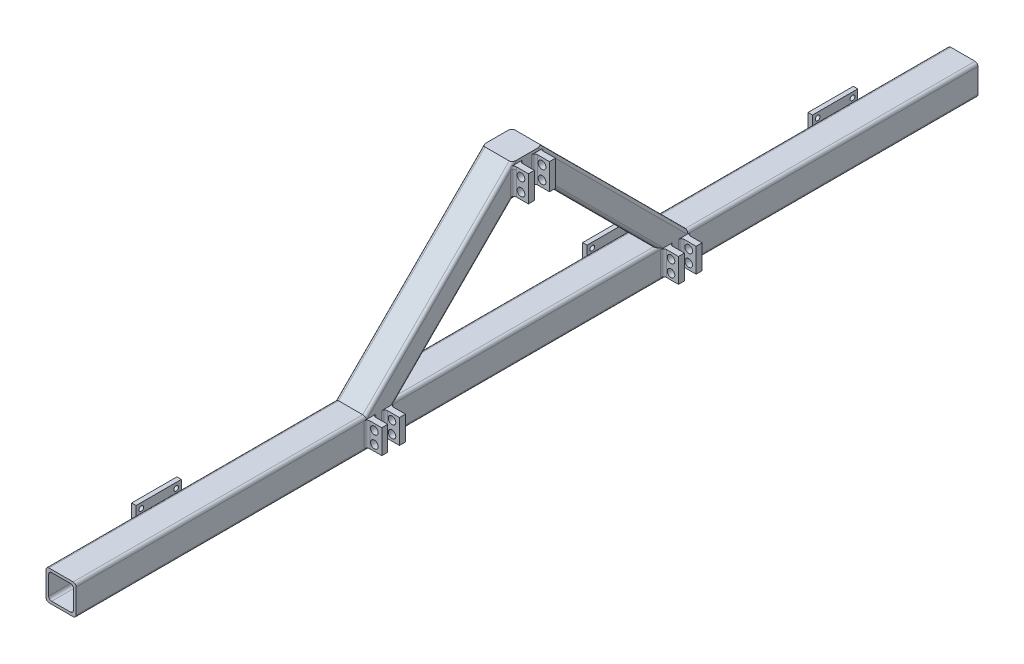
SolidWorks part; units mm, degrees
ref_plane "Alzado" through (0, 0, 0) normal (0, 0, 1) x (1, 0, 0)
ref_plane "Planta" through (0, 0, 0) normal (0, 1, 0) x (1, 0, 0)
ref_plane "Vista lateral" through (0, 0, 0) normal (1, 0, 0) x (0, 0, -1)
sketch "Croquis1" plane through (0, 0, 0) normal (0, 0, 1) x (1, 0, 0)
  line L1 (-40.8, 50.8) -> (40.8, 50.8)
  line L2 (-50.8, 40.8) -> (-50.8, -40.8)
  line L3 (-40.8, -50.8) -> (40.8, -50.8)
  line L4 (50.8, 40.8) -> (50.8, -40.8)
  line L5 (-31.8, 41.8) -> (31.8, 41.8)
  line L6 (-41.8, 31.8) -> (-41.8, -31.8)
  line L7 (-31.8, -41.8) -> (31.8, -41.8)
  line L8 (41.8, 31.8) -> (41.8, -31.8)
  arc A0 (40.8, -50.8) -> (50.8, -40.8) centre (40.8, -40.8) ccw
  arc A1 (31.8, -41.8) -> (41.8, -31.8) centre (31.8, -31.8) ccw
  arc A2 (-41.8, -31.8) -> (-31.8, -41.8) centre (-31.8, -31.8) ccw
  arc A3 (-50.8, -40.8) -> (-40.8, -50.8) centre (-40.8, -40.8) ccw
  arc A4 (31.8, 41.8) -> (41.8, 31.8) centre (31.8, 31.8) cw
  arc A5 (40.8, 50.8) -> (50.8, 40.8) centre (40.8, 40.8) cw
  arc A6 (-40.8, 50.8) -> (-50.8, 40.8) centre (-40.8, 40.8) ccw
  arc A7 (-31.8, 41.8) -> (-41.8, 31.8) centre (-31.8, 31.8) ccw
  point P8 (0, 41.8)
  point P10 (0, 50.8)
  point P11 (-41.8, 0)
  point P24 (50.8, 50.8)
  point P27 (-50.8, 50.8)
  dimension "D5" = 10
  dimension "D1" = 9
  dimension "D2" = 9
  dimension "D3" = 9
  dimension "D4" = 101.6
extrude "Saliente-Extruir1" add sketch "Croquis1" along normal blind 3040
sketch "Croquis2" plane through (50.8, 0, 0) normal (1, 0, 0) x (0, 0, -1)
  line L0 (0, 0) -> (-3040, 0) construction
  line L1 (-3040, -40.8) -> (-3040, 40.8) construction
  line L2 (-2073.8815, 40.8) -> (-1570, 544.6815)
  line L3 (-3040, 40.8) -> (0, 40.8) construction
  line L4 (-1570, 544.6815) -> (-1470, 544.6815)
  line L5 (-1470, 544.6815) -> (-966.1185, 40.8)
  line L6 (-1966.1185, 40.8) -> (-1570, 436.9185)
  line L7 (-1570, 436.9185) -> (-1470, 436.9185)
  line L8 (-1470, 436.9185) -> (-1073.8815, 40.8)
  line L9 (-1073.8815, 40.8) -> (-966.1185, 40.8)
  line L10 (-2073.8815, 40.8) -> (-1966.1185, 40.8)
  point P9 (-1520, 544.6815)
  point P12 (-1520, 0)
  point P13 (-2020, 40.8)
  point P16 (-1020, 40.8)
  dimension "D1" = 100
  dimension "D2" = 1000
  dimension "D3" = 76.2
  dimension "D4" = 45
extrude "Saliente-Extruir2" add sketch "Croquis2" against normal up to vertex (101.6 mm away) up to point (-50.8, 40.8, 3040)
fillet "Redondeo1" radius 10 1 edges at (-50.8, 292.7408, 1821.9408)
fillet "Redondeo2" radius 10 8 edges at (-50.8, 238.8592, 1271.9408) (-50.8, 436.9185, 1520) (50.8, 238.8592, 1768.0592) (50.8, 436.9185, 1520) (50.8, 238.8592, 1271.9408) (50.8, 292.7408, 1218.0592) (-50.8, 292.7408, 1218.0592) (50.8, 292.7408, 1821.9408)
sketch "Croquis3" plane through (50.8, 0, 0) normal (1, 0, 0) x (0, 0, -1)
  line L0 (-1574.1421, 446.9185) -> (-1465.8579, 446.9185) construction
  line L1 (-1565.5, 535.0394) -> (-1545.5, 535.0394)
  line L2 (-1565.5, 535.0394) -> (-1565.5, 446.9185)
  line L3 (-1565.5, 446.9185) -> (-1545.5, 446.9185)
  line L4 (-1545.5, 535.0394) -> (-1545.5, 446.9185)
  line L6 (-1494.5, 535.0394) -> (-1474.5, 535.0394)
  line L7 (-1494.5, 535.0394) -> (-1494.5, 446.9185)
  line L8 (-1494.5, 446.9185) -> (-1474.5, 446.9185)
  line L9 (-1474.5, 535.0394) -> (-1474.5, 446.9185)
  line L11 (-980.2606, 40.8) -> (-1484.1421, 544.6815) construction
  line L12 (-1555.8579, 544.6815) -> (-2059.7394, 40.8) construction
  dimension "D1" = 51
  dimension "D2" = 20
extrude "Saliente-Extruir3" add sketch "Croquis3" along normal blind 50
sketch "Croquis4" plane through (0, 0, 1565.5) normal (0, 0, 1) x (1, 0, 0)
  line L0 (75.8, 535.0394) -> (75.8, 446.9185) construction
  line L1 (100.8, 535.0394) -> (50.8, 535.0394) construction
  line L2 (100.8, 446.9185) -> (50.8, 446.9185) construction
  line L3 (50.8, 490.9789) -> (100.8, 490.9789) construction
  line L4 (50.8, 535.0394) -> (50.8, 446.9185) construction
  line L5 (100.8, 535.0394) -> (100.8, 446.9185) construction
  circle A0 centre (75.8, 513.0089) radius 13
  circle A1 centre (75.8, 468.9489) radius 13
  dimension "D1" = 26
  dimension "D2" = 44.06
extrude "Cortar-Extruir1" cut sketch "Croquis4" against normal through all
sketch "Croquis5" plane through (-50.8, 0, 0) normal (-1, 0, 0) x (0, 0, 1)
  line L0 (0, 0) -> (760, 0) construction
  line L1 (760, 0) -> (1520, 0) construction
  line L2 (1520, 0) -> (2280, 0) construction
  line L3 (2280, 0) -> (3040, 0) construction
  line L4 (3040, 40.8) -> (3040, -40.8) construction
  line L5 (976.1185, 50.8) -> (0, 50.8) construction
  line L6 (456.2, -76.2) -> (303.8, -76.2)
  line L7 (456.2, -76.2) -> (456.2, 76.2)
  line L8 (456.2, 76.2) -> (303.8, 76.2)
  line L9 (303.8, -76.2) -> (303.8, 76.2)
  line L10 (456.2, -76.2) -> (303.8, 76.2) construction
  line L11 (456.2, 76.2) -> (303.8, -76.2) construction
  line L12 (1216.2, -76.2) -> (1216.2, 76.2)
  line L13 (1216.2, -76.2) -> (1063.8, -76.2)
  line L14 (1063.8, -76.2) -> (1063.8, 76.2)
  line L15 (1216.2, 76.2) -> (1063.8, 76.2)
  line L16 (1976.2, -76.2) -> (1976.2, 76.2)
  line L17 (1976.2, -76.2) -> (1823.8, -76.2)
  line L18 (1823.8, -76.2) -> (1823.8, 76.2)
  line L19 (1976.2, 76.2) -> (1823.8, 76.2)
  line L20 (2736.2, -76.2) -> (2736.2, 76.2)
  line L21 (2736.2, -76.2) -> (2583.8, -76.2)
  line L22 (2583.8, -76.2) -> (2583.8, 76.2)
  line L23 (2736.2, 76.2) -> (2583.8, 76.2)
  line L24 (456.2, -76.2) -> (1216.2, -76.2) construction
  circle A1 centre (438.7375, 58.7375) radius 7.9375
  circle A2 centre (321.2625, 58.7375) radius 7.9375
  circle A3 centre (438.7375, -58.7375) radius 7.9375
  circle A4 centre (321.2625, -58.7375) radius 7.9375
  circle A5 centre (1198.7375, 58.7375) radius 7.9375
  circle A6 centre (1081.2625, 58.7375) radius 7.9375
  circle A7 centre (1081.2625, -58.7375) radius 7.9375
  circle A8 centre (1198.7375, -58.7375) radius 7.9375
  circle A9 centre (1958.7375, 58.7375) radius 7.9375
  circle A10 centre (1841.2625, 58.7375) radius 7.9375
  circle A11 centre (1841.2625, -58.7375) radius 7.9375
  circle A12 centre (1958.7375, -58.7375) radius 7.9375
  circle A13 centre (2718.7375, 58.7375) radius 7.9375
  circle A14 centre (2601.2625, 58.7375) radius 7.9375
  circle A15 centre (2601.2625, -58.7375) radius 7.9375
  circle A16 centre (2718.7375, -58.7375) radius 7.9375
  point P3 (380, 0)
  point P13 (1140, 0)
  point P14 (438.7375, -58.7375)
  point P15 (321.2625, -58.7375)
  point P18 (1900, 0)
  point P23 (2660, 0)
  point P66 (321.2625, 58.7375)
  point P67 (438.7375, 58.7375)
  point P68 (438.7375, 58.7375)
  point P69 (321.2625, 58.7375)
  point P70 (321.2625, -58.7375)
  dimension "D2" = 15.875
  dimension "D1" = 152.4
  dimension "D3" = 4
  dimension "D4" = 760
extrude "Saliente-Extruir4" add sketch "Croquis5" along normal blind 15
sketch "Croquis6" plane through (50.8, 0, 0) normal (1, 0, 0) x (0, 0, -1)
  line L0 (-3040, -40.8) -> (0, -40.8) construction
  line L1 (-2059.7394, 40.8) -> (-2039.7394, 40.8)
  line L2 (-2059.7394, 40.8) -> (-2059.7394, -40.8)
  line L3 (-2059.7394, -40.8) -> (-2039.7394, -40.8)
  line L4 (-2039.7394, 40.8) -> (-2039.7394, -40.8)
  line L6 (-1980.2606, 40.8) -> (-2000.2606, 40.8)
  line L7 (-1980.2606, 40.8) -> (-1980.2606, -40.8)
  line L8 (-1980.2606, -40.8) -> (-2000.2606, -40.8)
  line L9 (-2000.2606, 40.8) -> (-2000.2606, -40.8)
  line L10 (-1520, 544.6815) -> (-1520, -40.8) construction
  line L11 (-1484.1421, 544.6815) -> (-1555.8579, 544.6815) construction
  line L12 (-1059.7394, -40.8) -> (-1039.7394, -40.8)
  line L13 (-1039.7394, 40.8) -> (-1039.7394, -40.8)
  line L14 (-1059.7394, 40.8) -> (-1039.7394, 40.8)
  line L15 (-1059.7394, 40.8) -> (-1059.7394, -40.8)
  line L16 (-980.2606, -40.8) -> (-1000.2606, -40.8)
  line L17 (-1000.2606, 40.8) -> (-1000.2606, -40.8)
  line L18 (-980.2606, 40.8) -> (-1000.2606, 40.8)
  line L19 (-980.2606, 40.8) -> (-980.2606, -40.8)
  dimension "D1" = 20
extrude "Saliente-Extruir5" add sketch "Croquis6" along normal blind 50
sketch "Croquis7" plane through (0, 0, 2059.7394) normal (0, 0, 1) x (1, 0, 0)
  line L0 (100.8, 40.8) -> (100.8, 0) construction
  line L1 (100.8, 40.8) -> (100.8, -40.8) construction
  line L2 (50.8, 40.8) -> (100.8, 40.8) construction
  line L3 (100.8, 0) -> (50.8, 0) construction
  circle A0 centre (75.8, 20.4) radius 12.7
  circle A1 centre (75.8, -20.4) radius 12.7
  point P9 (75.8, 40.8)
  point P12 (100.8, 20.4)
  dimension "D1" = 25.4
extrude "Cortar-Extruir2" cut sketch "Croquis7" against normal through all
fillet "Redondeo3" radius 10 4 edges at (50.8, 490.9789, 1565.5) (50.8, 490.9789, 1545.5) (50.8, 490.9789, 1494.5) (50.8, 490.9789, 1474.5)
fillet "Redondeo4" radius 10 8 edges at (50.8, 0, 2059.7394) (50.8, 0, 2000.2606) (50.8, 0, 1980.2606) (50.8, 0, 2039.7394) (50.8, 0, 1039.7394) (50.8, 0, 1000.2606) (50.8, 0, 980.2606) (50.8, 0, 1059.7394)
